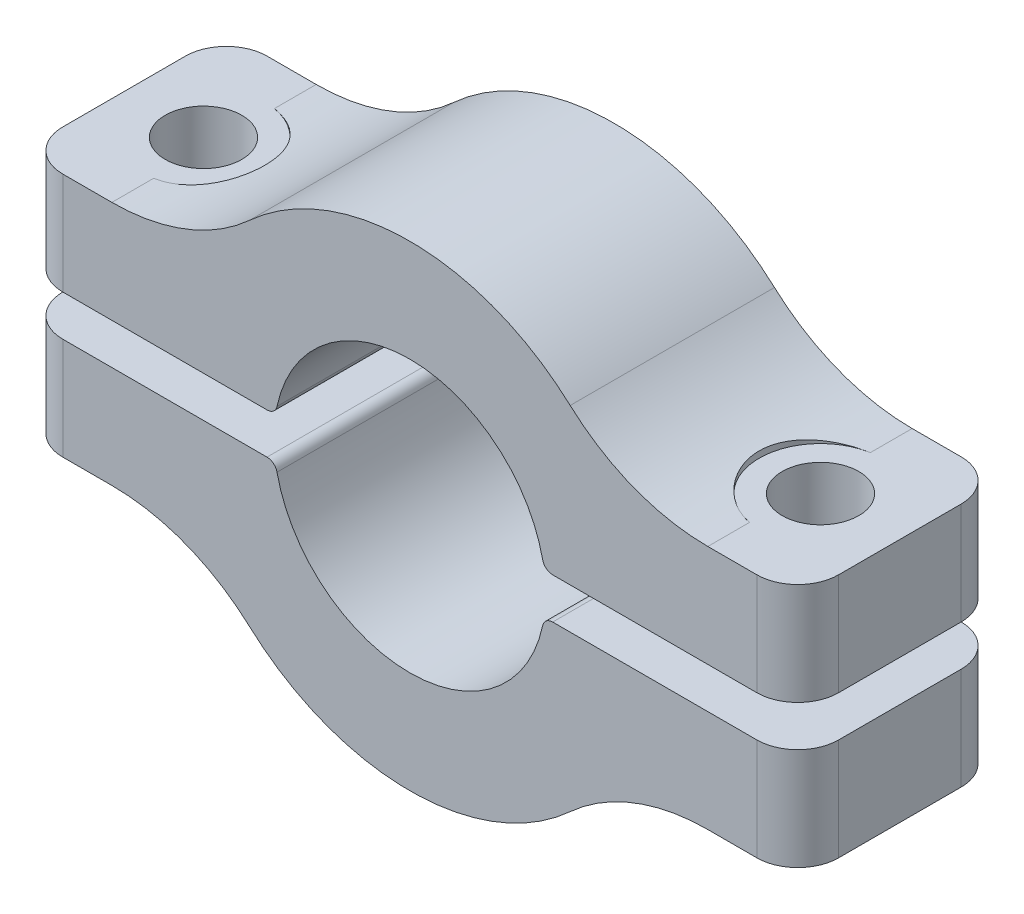
SolidWorks part; units mm, degrees
ref_plane "Front Plane" through (0, 0, 0) normal (0, 0, 1) x (1, 0, 0)
ref_plane "Top Plane" through (0, 0, 0) normal (0, 1, 0) x (1, 0, 0)
ref_plane "Right Plane" through (0, 0, 0) normal (1, 0, 0) x (0, 0, -1)
sketch "Sketch1" plane through (0, 0, 0) normal (0, 0, 1) x (1, 0, 0)
  line L0 (-18.9861, 1) -> (-6.5744, 1)
  line L1 (6.5744, 1) -> (18.9861, 1)
  line L2 (18.9861, 1) -> (18.9861, 6)
  line L3 (18.9861, 6) -> (9.9861, 6)
  line L4 (-9.9861, 6) -> (-18.9861, 6)
  line L5 (-18.9861, 6) -> (-18.9861, 1)
  line L6 (0, -5.5) -> (0, 5.5) construction
  arc A0 (-6.5744, 1) -> (6.5744, 1) centre (0, 0) cw
  arc A2 (-9.9861, 6) -> (9.9861, 6) centre (0, 0) cw
  dimension "D2" = 6.65
  dimension "D1" = 5
  dimension "D3" = 5
  dimension "D4" = 9
  dimension "D5" = 9
  dimension "D6" = 1
extrude "Boss-Extrude1" add sketch "Sketch1" along normal blind 10
fillet "Fillet1" radius 2 4 edges at (18.9861, 3.5, 0) (-18.9861, 3.5, 0) (18.9861, 3.5, 10) (-18.9861, 3.5, 10)
fillet "Fillet3" radius 0.5 2 edges at (-6.5744, 1, 5) (6.5744, 1, 5)
fillet "Fillet4" radius 10 2 edges at (9.9861, 6, 5) (-9.9861, 6, 5)
sketch "Sketch2" plane through (0, 0, 0) normal (0, 1, 0) x (1, 0, 0)
  line L1 (-12.815, 0) -> (12.815, 0) construction
  line L2 (0, -5.5) -> (0, 5.5) construction
  circle A0 centre (-15.1, -5) radius 1.875
  circle A1 centre (15.1, -5) radius 1.875
  point P2 (-15.504, -4.6877)
  point P5 (0, 0)
  point P7 (-15.504, -5)
  dimension "D1" = 3.75
  dimension "D2" = 5
  dimension "D3" = 15.1
extrude "Cut-Extrude1" cut sketch "Sketch2" along normal through all
sketch "Sketch3" plane through (0, 0, 0) normal (0, 1, 0) x (1, 0, 0)
  line L0 (0, -5.5) -> (0, 5.5) construction
  circle A0 centre (-15.1, -5) radius 3
  circle A1 centre (15.1, -5) radius 3
  dimension "D1" = 6
extrude "Cut-Extrude2" cut sketch "Sketch3" along normal blind 10 from offset 6
mirror "Mirror3" about plane through (0, 0, 0) normal (0, 1, 0) of bodies 107 101
equation "\"shaftDiameter\"= 12.7mm"
equation "\"D2@Sketch1\"=\"shaftDiameter\"/2 +0.3"
equation "\"holeDiameter\"= 3.75mm"
equation "\"D1@Sketch2\"=3.75"
